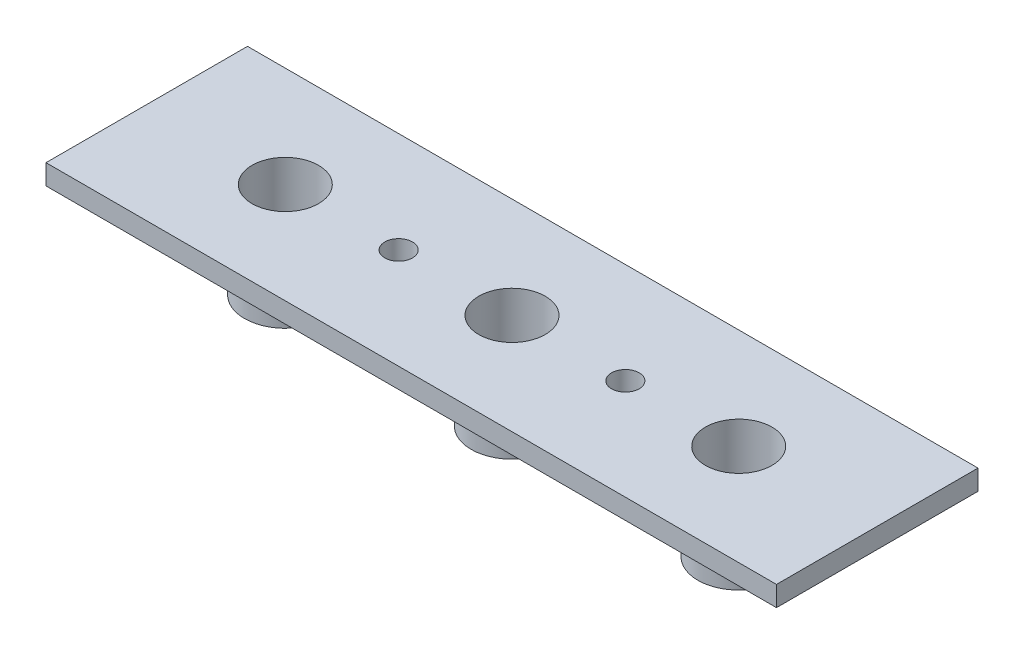
SolidWorks part; units mm, degrees
ref_plane "Płaszczyzna przednia" through (0, 0, 0) normal (0, 0, 1) x (1, 0, 0)
ref_plane "Płaszczyzna górna" through (0, 0, 0) normal (0, 1, 0) x (1, 0, 0)
ref_plane "Płaszczyzna prawa" through (0, 0, 0) normal (1, 0, 0) x (0, 0, -1)
sketch "Sketch2" plane through (0, 0, 0) normal (0, 1, 0) x (1, 0, 0)
  line L0 (0, 0) -> (135.8153, 0) construction
  line L1 (45, 31.2672) -> (45, -27.2453) construction
  line L2 (-27.5, 20) -> (117.5, 20)
  line L3 (-27.5, 20) -> (-27.5, -20)
  line L4 (-27.5, 0) -> (117.5, 0)
  line L5 (45, 20) -> (45, 0)
  line L6 (117.5, 20) -> (117.5, -20)
  line L7 (-27.5, -20) -> (117.5, -20)
  circle A0 centre (0, 0) radius 8.4 construction
  circle A3 centre (0, 0) radius 8.1
  circle A4 centre (0, 0) radius 6.6
  circle A5 centre (45, 0) radius 6.6
  circle A6 centre (45, 0) radius 8.1
  circle A7 centre (45, 0) radius 8.4 construction
  circle A8 centre (90, 0) radius 6.6
  circle A9 centre (90, 0) radius 8.1
  circle A10 centre (90, 0) radius 8.4 construction
  dimension "D1" = 16.8
  dimension "D5" = 1.5
  dimension "D2" = 16.2
  dimension "D3" = 72.5
  dimension "D4" = 20
  dimension "D6" = 3
extrude "Boss-Extrude3" add sketch "Sketch2" along normal blind 4 contours A6 L5 L2 L3 L4 A3 | A4 L4 A3 | A4 L4 A3 | L5 A6 L4 A5 | L4 A6 L5 A5 | L4 A6 A5 | L4 A9 A8 | L4 A9 A8 | A9 L4 L6 L2 L5 A6 | A9 L4 A6 A3 L3 L7 L6 region at (8.1409, 0, -10.7831) region at (81.8591, 0, -10.7831) region at (45, 0, 10.7831) region at (49.6954, 0, -4.6954) region at (40.3046, 0, -4.6954) region at (0, 0, -7.9189) region at (-7.35, 0, 0.1811) region at (45, 0, 7.9189) region at (90, 0, 7.9189) region at (97.35, 0, -0.1811)
extrude "Boss-Extrude4" add sketch "Sketch2<5>" against normal blind 15 contours A4 L4 A3 | A4 L4 A3 | L5 A6 L4 A5 | L4 A6 L5 A5 | L4 A6 A5 | L4 A9 A8 | L4 A9 A8 region at (49.6954, 0, -4.6954) region at (40.3046, 0, -4.6954) region at (0, 0, -7.9189) region at (-7.35, 0, 0.1811) region at (45, 0, 7.9189) region at (90, 0, 7.9189) region at (97.35, 0, -0.1811)
sketch "Sketch2<5>" plane through (0, 0, 0) normal (0, 1, 0) x (1, 0, 0) same geometry as "Sketch2"
sketch "Sketch3" plane through (0, 0, 0) normal (0, -1, 0) x (1, 0, 0)
  line L0 (0, 0) -> (45, 0) construction
  circle A0 centre (45, 0) radius 6.6 construction
  circle A1 centre (22.5, 0) radius 2.75
  circle A2 centre (22.5, 0) radius 7
  circle A3 centre (67.5, 0) radius 7
  circle A4 centre (67.5, 0) radius 2.75
  dimension "D1" = 5.5
  dimension "D2" = 14
  dimension "D3" = 2
extrude "Cut-Extrude1" cut sketch "Sketch3" against normal blind 74 contours L0 A1 | A1 L0 | A4 region at (22.5, 0, -1.1671) region at (22.5, 0, 1.1671) region at (67.5, 0, 0)
